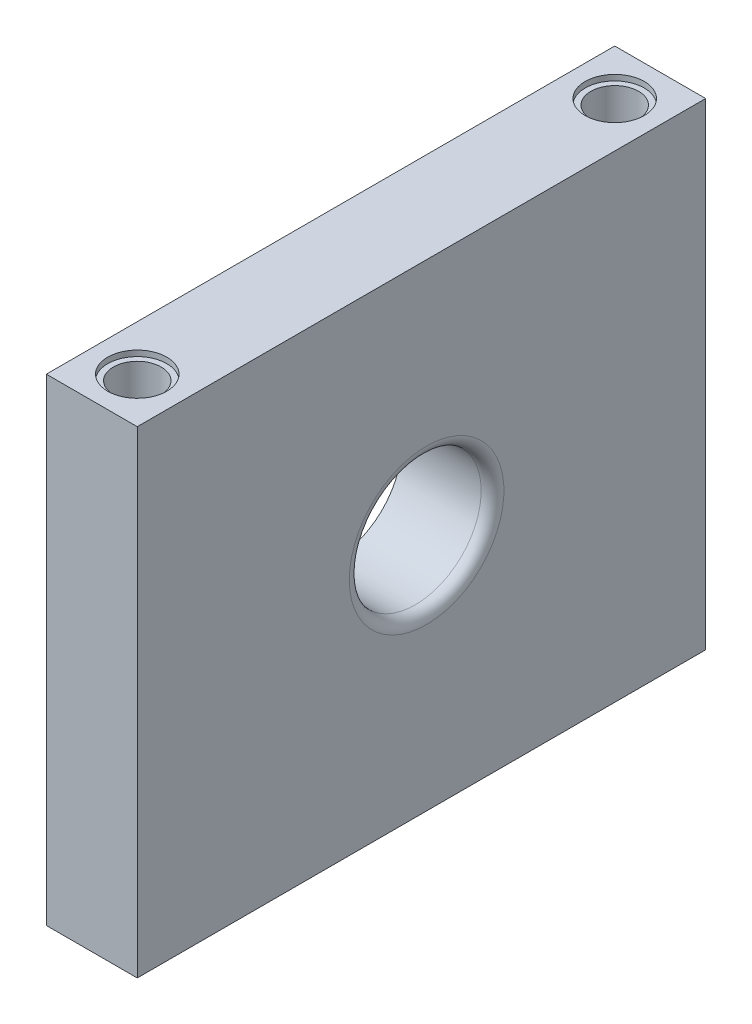
SolidWorks part; units mm, degrees
ref_plane "Front Plane" through (0, 0, 0) normal (0, 0, 1) x (1, 0, 0)
ref_plane "Top Plane" through (0, 0, 0) normal (0, 1, 0) x (1, 0, 0)
ref_plane "Right Plane" through (0, 0, 0) normal (1, 0, 0) x (0, 0, -1)
sketch "Sketch1" plane through (0, 0, 0) normal (0, 1, 0) x (1, 0, 0)
  line L1 (-10.223, 36.3848) -> (14.777, 36.3848)
  line L2 (-10.223, 36.3848) -> (-10.223, -13.6152)
  line L3 (-10.223, -13.6152) -> (14.777, -13.6152)
  line L4 (14.777, 36.3848) -> (14.777, -13.6152)
  circle A0 centre (1.277, 11.3848) radius 3.4
  dimension "D3" = 6.8
  dimension "D1" = 50
  dimension "D2" = 25
  dimension "D4" = 13.5
  dimension "D5" = 25
extrude "Boss-Extrude1" add sketch "Sketch1" along normal blind 3
sketch "Sketch2" plane through (-10.223, 0, 0) normal (-1, 0, 0) x (0, 0, 1)
  line L0 (18.15, 0) -> (-18.15, 0) construction
  line L1 (-36.3848, 3) -> (13.6152, 3)
  line L2 (-36.3848, 3) -> (-36.3848, 0)
  line L3 (-36.3848, 0) -> (13.6152, 0)
  line L4 (13.6152, 3) -> (13.6152, 0)
  line L5 (13.6152, 3) -> (13.6152, 0) construction
extrude "Boss-Extrude2" add sketch "Sketch2" along normal blind 8
sketch "Sketch3" plane through (0, 0, 0) normal (0, -1, 0) x (1, 0, 0)
  line L0 (-18.223, 13.6152) -> (14.777, 13.6152) construction
  line L1 (-18.223, -36.3848) -> (-10.223, -36.3848)
  line L2 (-18.223, -36.3848) -> (-18.223, 13.6152)
  line L3 (-18.223, 13.6152) -> (-10.223, 13.6152)
  line L4 (-10.223, -36.3848) -> (-10.223, 13.6152)
  dimension "D1" = 8
extrude "Boss-Extrude3" add sketch "Sketch3" along normal blind 42
sketch "Sketch4" plane through (0, 3, 0) normal (0, 1, 0) x (1, 0, 0)
  line L0 (-18.223, -13.6152) -> (-18.223, 36.3848) construction
  line L1 (14.777, 36.3848) -> (-18.223, 36.3848) construction
  line L2 (-18.223, -13.6152) -> (14.777, -13.6152) construction
  circle A0 centre (-14.223, 32.3848) radius 2.65
  circle A1 centre (-14.223, -9.6152) radius 2.65
  dimension "D2" = 5.3
  dimension "D4" = 5.3
  dimension "D5" = 4
  dimension "D6" = 4
  dimension "D1" = 4
  dimension "D3" = 4
extrude "Cut-Extrude1" cut sketch "Sketch4" against normal blind 0.5
ref_plane "Plane1" through (0, -19.5, 0) normal (0, 1, 0) x (1, 0, 0)
mirror "Mirror1" about plane through (0, -19.5, 0) normal (0, 1, 0) of "Cut-Extrude1"
sketch "Sketch5" plane through (-18.223, 0, 0) normal (-1, 0, 0) x (0, 0, 1)
  line L0 (18.15, 0) -> (-18.15, 0) construction
  line L1 (-6.9841, -24.1818) -> (-6.6547, -18.3888) construction
  line L2 (-6.6547, -18.3888) -> (-11.5069, -15.207) construction
  line L3 (-11.5069, -15.207) -> (-16.6885, -17.8182) construction
  line L4 (-16.6885, -17.8182) -> (-17.0179, -23.6112) construction
  line L5 (-17.0179, -23.6112) -> (-12.1657, -26.793) construction
  line L6 (-12.1657, -26.793) -> (-6.9841, -24.1818) construction
  circle A0 centre (-11.8363, -21) radius 5.025 construction
  circle A1 centre (-11.8363, -21) radius 5.8024
  dimension "D1" = 21
  dimension "D2" = 10.05
extrude "Cut-Extrude2" cut sketch "Sketch5" against normal blind 9
fillet "Fillet2" radius 1 1 edges at (-10.223, -21, -6.0339)
ref_plane "Plane2" through (-1.723, 0, 0) normal (-1, 0, 0) x (0, 0, 1)
mirror "Mirror2" about plane through (-1.723, 0, 0) normal (-1, 0, 0) of "Cut-Extrude1"
sketch "Sketch6" plane through (0, 3, 0) normal (0, 1, 0) x (1, 0, 0)
  line L0 (1.277, 14.7848) -> (1.277, 7.9848) construction
  line L1 (14.777, -13.6152) -> (14.777, 36.3848) construction
  line L2 (14.777, 16.9444) -> (14.777, 5.8251)
  circle A0 centre (1.277, 11.3848) radius 3.4 construction
  circle A1 centre (1.277, 11.3848) radius 3.1
  circle A2 centre (1.277, 11.3848) radius 12.6
  arc A3 (14.777, 16.9444) -> (14.777, 5.8251) centre (1.277, 11.3848) ccw
  line M9 (14.777, -13.6152) -> (14.777, 36.3848)
  dimension "D1" = 25.2
  dimension "D2" = 2
extrude "Boss-Extrude4" add sketch "Sketch6" along normal blind 2 contours A3 A2 M9
fillet "Fillet4" radius 1 1 edges at (14.777, 5, -11.3848)
sketch "Sketch8" plane through (0, 3, 0) normal (0, 1, 0) x (1, 0, 0)
  line L0 (4.677, 11.3848) -> (-2.123, 11.3848) construction
  circle A0 centre (1.277, 11.3848) radius 3.4 construction
  circle A1 centre (1.277, 19.8848) radius 1.5898
  circle A2 centre (1.277, 2.8848) radius 1.7774
  point P9 (1.277, 11.3848)
  dimension "D1" = 8.5
  dimension "D2" = 8.5
extrude "Cut-Extrude3" cut sketch "Sketch8" against normal blind 10
sketch "Sketch9" plane through (0, 0, 13.6152) normal (0, 0, 1) x (1, 0, 0)
  line L1 (14.777, 0) -> (-34.2447, 0)
  line L2 (14.777, 0) -> (14.777, 20.9769)
  line L3 (14.777, 20.9769) -> (-34.2447, 20.9769)
  line L4 (-34.2447, 0) -> (-34.2447, 20.9769)
extrude "Cut-Extrude4" cut sketch "Sketch9" against normal through all
ref_plane "Plane3" through (0, 0, -11.3848) normal (0, 0, 1) x (1, 0, 0)
sketch "Sketch11" plane through (0, 0, 0) normal (0, 1, 0) x (1, 0, 0)
  circle A2 centre (-14.223, 32.3848) radius 2.1
  dimension "D1" = 4.2
extrude "Cut-Extrude5" cut sketch "Sketch11" against normal through all contours A2
mirror "Mirror3" about plane through (0, 0, -11.3848) normal (0, 0, 1) of "Cut-Extrude5"
sketch "Sketch14" plane through (0, 0, 0) normal (0, 1, 0) x (1, 0, 0)
  circle A0 centre (-14.223, -9.6152) radius 2.6
  dimension "D1" = 5.2
extrude "Cut-Extrude6" cut sketch "Sketch14" against normal blind 0.5
mirror "Mirror4" about plane through (0, 0, -11.3848) normal (0, 0, 1) of "Cut-Extrude6"
